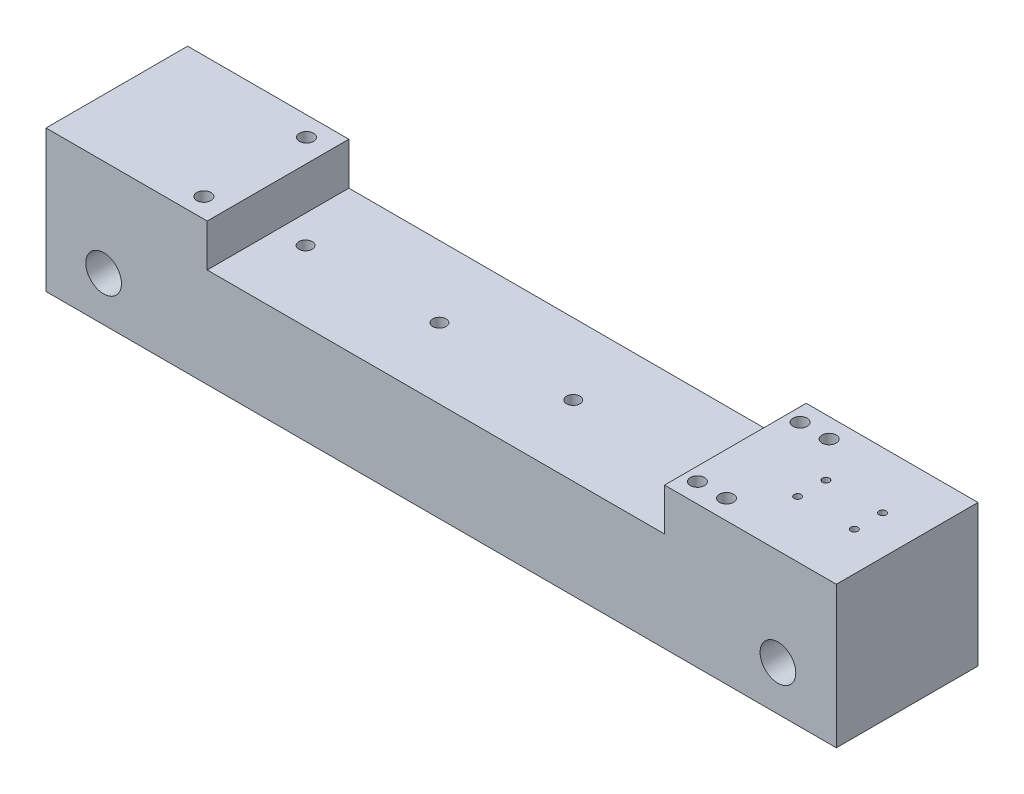
SolidWorks part; units mm, degrees
material "McMaster Steel"
ref_plane "Front Plane" through (0, 0, 0) normal (0, 0, 1) x (1, 0, 0)
ref_plane "Top Plane" through (0, 0, 0) normal (0, 1, 0) x (1, 0, 0)
ref_plane "Right Plane" through (0, 0, 0) normal (1, 0, 0) x (0, 0, -1)
sketch "Sketch1" plane through (0, 0, 0) normal (0, 0, 1) x (1, 0, 0)
  line L0 (177.125, 59) -> (177.125, 63.5)
  line L1 (177.125, 63.5) -> (100.125, 63.5)
  line L2 (100.125, 63.5) -> (100.125, 59)
  line L3 (100.125, 44.5) -> (-104.875, 44.5)
  line L4 (-2.375, 44.5) -> (-2.375, 40)
  line L5 (-104.875, 63.5) -> (-177.125, 63.5)
  line L6 (-177.125, 63.5) -> (-177.125, 59)
  line L7 (-104.875, 63.5) -> (-104.875, 59)
  circle A0 centre (164.385, 33.435) radius 2.6035
  circle A1 centre (169.95, 20) radius 2.6035
  circle A2 centre (164.385, 6.565) radius 2.6035
  circle A3 centre (137.515, 6.565) radius 2.6035
  circle A4 centre (131.95, 20) radius 2.6035
  circle A5 centre (137.515, 33.435) radius 2.6035
  circle A6 centre (-137.865, 33.435) radius 2.6035
  circle A7 centre (-132.3, 20) radius 2.6035
  circle A8 centre (-137.865, 6.565) radius 2.6035
  circle A9 centre (-164.735, 6.565) radius 2.6035
  circle A10 centre (-170.3, 20) radius 2.6035
  circle A11 centre (-164.735, 33.435) radius 2.6035
  line B0 (-177.125, 0) -> (177.125, 0)
  line B1 (177.125, 0) -> (177.125, 59)
  line B2 (177.125, 59) -> (100.125, 59)
  line B3 (100.125, 59) -> (100.125, 40)
  line B4 (100.125, 40) -> (-104.875, 40)
  line B5 (-104.875, 40) -> (-104.875, 59)
  line B6 (-104.875, 59) -> (-177.125, 59)
  line B7 (-177.125, 59) -> (-177.125, 0)
  circle B8 centre (-151.3, 20) radius 14
  circle B9 centre (150.95, 20) radius 14
  arc B10 (-164.735, 9.315) -> (-164.735, 3.815) centre (-164.735, 6.565) ccw
  arc B11 (-164.735, 9.315) -> (-164.735, 3.815) centre (-164.735, 6.565) ccw
  arc B12 (-164.735, 3.815) -> (-164.735, 9.315) centre (-164.735, 6.565) ccw
  arc B13 (-164.735, 3.815) -> (-164.735, 9.315) centre (-164.735, 6.565) ccw
  arc B14 (-137.865, 3.815) -> (-137.865, 9.315) centre (-137.865, 6.565) ccw
  arc B15 (-137.865, 3.815) -> (-137.865, 9.315) centre (-137.865, 6.565) ccw
  arc B16 (-137.865, 9.315) -> (-137.865, 3.815) centre (-137.865, 6.565) ccw
  arc B17 (-137.865, 9.315) -> (-137.865, 3.815) centre (-137.865, 6.565) ccw
  arc B18 (-132.3, 17.25) -> (-132.3, 22.75) centre (-132.3, 20) ccw
  arc B19 (-132.3, 17.25) -> (-132.3, 22.75) centre (-132.3, 20) ccw
  arc B20 (-132.3, 22.75) -> (-132.3, 17.25) centre (-132.3, 20) ccw
  arc B21 (-132.3, 22.75) -> (-132.3, 17.25) centre (-132.3, 20) ccw
  arc B22 (-137.865, 30.685) -> (-137.865, 36.185) centre (-137.865, 33.435) ccw
  arc B23 (-137.865, 30.685) -> (-137.865, 36.185) centre (-137.865, 33.435) ccw
  arc B24 (-137.865, 36.185) -> (-137.865, 30.685) centre (-137.865, 33.435) ccw
  arc B25 (-137.865, 36.185) -> (-137.865, 30.685) centre (-137.865, 33.435) ccw
  arc B26 (-170.3, 17.25) -> (-170.3, 22.75) centre (-170.3, 20) ccw
  arc B27 (-170.3, 17.25) -> (-170.3, 22.75) centre (-170.3, 20) ccw
  arc B28 (-170.3, 22.75) -> (-170.3, 17.25) centre (-170.3, 20) ccw
  arc B29 (-170.3, 22.75) -> (-170.3, 17.25) centre (-170.3, 20) ccw
  arc B30 (-164.735, 30.685) -> (-164.735, 36.185) centre (-164.735, 33.435) ccw
  arc B31 (-164.735, 30.685) -> (-164.735, 36.185) centre (-164.735, 33.435) ccw
  arc B32 (-164.735, 36.185) -> (-164.735, 30.685) centre (-164.735, 33.435) ccw
  arc B33 (-164.735, 36.185) -> (-164.735, 30.685) centre (-164.735, 33.435) ccw
  arc B34 (137.515, 9.315) -> (137.515, 3.815) centre (137.515, 6.565) ccw
  arc B35 (137.515, 9.315) -> (137.515, 3.815) centre (137.515, 6.565) ccw
  arc B36 (137.515, 3.815) -> (137.515, 9.315) centre (137.515, 6.565) ccw
  arc B37 (137.515, 3.815) -> (137.515, 9.315) centre (137.515, 6.565) ccw
  arc B38 (164.385, 9.315) -> (164.385, 3.815) centre (164.385, 6.565) ccw
  arc B39 (164.385, 9.315) -> (164.385, 3.815) centre (164.385, 6.565) ccw
  arc B40 (164.385, 3.815) -> (164.385, 9.315) centre (164.385, 6.565) ccw
  arc B41 (164.385, 3.815) -> (164.385, 9.315) centre (164.385, 6.565) ccw
  arc B42 (169.95, 17.25) -> (169.95, 22.75) centre (169.95, 20) ccw
  arc B43 (169.95, 17.25) -> (169.95, 22.75) centre (169.95, 20) ccw
  arc B44 (169.95, 22.75) -> (169.95, 17.25) centre (169.95, 20) ccw
  arc B45 (169.95, 22.75) -> (169.95, 17.25) centre (169.95, 20) ccw
  arc B46 (164.385, 30.685) -> (164.385, 36.185) centre (164.385, 33.435) ccw
  arc B47 (164.385, 30.685) -> (164.385, 36.185) centre (164.385, 33.435) ccw
  arc B48 (164.385, 36.185) -> (164.385, 30.685) centre (164.385, 33.435) ccw
  arc B49 (164.385, 36.185) -> (164.385, 30.685) centre (164.385, 33.435) ccw
  arc B50 (131.95, 17.25) -> (131.95, 22.75) centre (131.95, 20) ccw
  arc B51 (131.95, 17.25) -> (131.95, 22.75) centre (131.95, 20) ccw
  arc B52 (131.95, 22.75) -> (131.95, 17.25) centre (131.95, 20) ccw
  arc B53 (131.95, 22.75) -> (131.95, 17.25) centre (131.95, 20) ccw
  arc B54 (137.515, 30.685) -> (137.515, 36.185) centre (137.515, 33.435) ccw
  arc B55 (137.515, 30.685) -> (137.515, 36.185) centre (137.515, 33.435) ccw
  arc B56 (137.515, 36.185) -> (137.515, 30.685) centre (137.515, 33.435) ccw
  arc B57 (137.515, 36.185) -> (137.515, 30.685) centre (137.515, 33.435) ccw
  dimension "D1" = 5.207
  dimension "D2" = 63.5
sketch_block_instance "Block-SecondaryBlock Sideview-1"
sketch_block "Block-SecondaryBlock Sideview"
extrude "Boss-Extrude1" add sketch "Sketch1" along normal blind 63.5 contours B6 B7 B0 B1 B2 B3 B4 B5 B56 B54 B52 B50 B48 B46 B44 B42 B40 B38 B36 B34 B32 B30 B28 B26 B24 B22 B20 B18 B16 B14 B12 B10 B9 B8 | B46 B48 A0 | B54 B56 A5 | B42 B44 A1 | B38 B40 A2 | B50 B52 A4 | B34 B36 A3 | B22 B24 A6 | B18 B20 A7 | B14 B16 A8 | B10 B12 A9 | B26 B28 A10 | B30 B32 A11 | B2 L0 L1 L2 | B4 B3 L3 L4 | B6 L7 L5 L6 | B5 B4 L4 L3 region at (138.625, 61.25, 0) region at (0.6144, 25.4009, 0) region at (48.875, 42.25, 0) region at (-141, 61.25, 0) region at (-53.625, 42.25, 0) region at (-162.0628, 6.565, 0) region at (-140.5372, 6.565, 0) region at (-134.9722, 20, 0) region at (-140.5372, 33.435, 0) region at (-172.9722, 20, 0) region at (-167.4072, 33.435, 0) region at (140.1872, 6.565, 0) region at (167.0572, 6.565, 0) region at (167.2778, 20, 0) region at (161.7128, 33.435, 0) region at (129.2778, 20, 0) region at (134.8428, 33.435, 0)
sketch "Sketch2" plane through (0, 63.5, 0) normal (0, 1, 0) x (1, 0, 0)
  line L0 (177.125, -61.75) -> (177.125, -1.75)
  line L2 (177.125, -63.5) -> (177.125, 0) construction
  circle A0 centre (119.125, -54.75) radius 3.175
  circle A1 centre (106.125, -54.75) radius 3.175
  circle A2 centre (119.125, -8.75) radius 3.175
  circle A3 centre (106.125, -8.75) radius 3.175
  circle A4 centre (-115.125, -54.75) radius 3.175
  circle A5 centre (-115.125, -8.75) radius 3.175
  point P13 (177.125, -31.75)
  point P20 (177.125, -31.75)
  line B0 (-177.125, -1.75) -> (177.125, -1.75)
  line B1 (177.125, -1.75) -> (177.125, -41.55)
  line B2 (177.125, -41.55) -> (-177.125, -41.55) construction
  line B3 (-177.125, -41.55) -> (-177.125, -1.75)
  line B4 (-177.125, -41.55) -> (-177.125, -61.75)
  line B5 (-177.125, -61.75) -> (177.125, -61.75)
  line B6 (177.125, -61.75) -> (177.125, -41.55)
  arc B7 (-118.425, -8.75) -> (-111.825, -8.75) centre (-115.125, -8.75) ccw
  arc B8 (-111.825, -8.75) -> (-118.425, -8.75) centre (-115.125, -8.75) ccw
  arc B9 (-118.425, -54.75) -> (-111.825, -54.75) centre (-115.125, -54.75) ccw
  arc B10 (-111.825, -54.75) -> (-118.425, -54.75) centre (-115.125, -54.75) ccw
  arc B11 (-132.725, -34.65) -> (-128.525, -34.65) centre (-130.625, -34.65) ccw
  arc B12 (-128.525, -34.65) -> (-132.725, -34.65) centre (-130.625, -34.65) ccw
  arc B13 (-132.725, -8.65) -> (-128.525, -8.65) centre (-130.625, -8.65) ccw
  arc B14 (-128.525, -8.65) -> (-132.725, -8.65) centre (-130.625, -8.65) ccw
  arc B15 (-173.725, -34.65) -> (-169.525, -34.65) centre (-171.625, -34.65) ccw
  arc B16 (-169.525, -34.65) -> (-173.725, -34.65) centre (-171.625, -34.65) ccw
  arc B17 (-173.725, -8.65) -> (-169.525, -8.65) centre (-171.625, -8.65) ccw
  arc B18 (-169.525, -8.65) -> (-173.725, -8.65) centre (-171.625, -8.65) ccw
  arc B19 (128.525, -8.65) -> (132.725, -8.65) centre (130.625, -8.65) ccw
  arc B20 (132.725, -8.65) -> (128.525, -8.65) centre (130.625, -8.65) ccw
  arc B21 (169.525, -8.65) -> (173.725, -8.65) centre (171.625, -8.65) ccw
  arc B22 (173.725, -8.65) -> (169.525, -8.65) centre (171.625, -8.65) ccw
  arc B23 (169.525, -34.65) -> (173.725, -34.65) centre (171.625, -34.65) ccw
  arc B24 (173.725, -34.65) -> (169.525, -34.65) centre (171.625, -34.65) ccw
  arc B25 (128.525, -34.65) -> (132.725, -34.65) centre (130.625, -34.65) ccw
  arc B26 (132.725, -34.65) -> (128.525, -34.65) centre (130.625, -34.65) ccw
  arc B27 (115.825, -54.75) -> (122.425, -54.75) centre (119.125, -54.75) ccw
  arc B28 (122.425, -54.75) -> (115.825, -54.75) centre (119.125, -54.75) ccw
  arc B29 (102.825, -54.75) -> (109.425, -54.75) centre (106.125, -54.75) ccw
  arc B30 (109.425, -54.75) -> (102.825, -54.75) centre (106.125, -54.75) ccw
  arc B31 (115.825, -8.75) -> (122.425, -8.75) centre (119.125, -8.75) ccw
  arc B32 (122.425, -8.75) -> (115.825, -8.75) centre (119.125, -8.75) ccw
  arc B33 (102.825, -8.75) -> (109.425, -8.75) centre (106.125, -8.75) ccw
  arc B34 (109.425, -8.75) -> (102.825, -8.75) centre (106.125, -8.75) ccw
  dimension "D1" = 6.35
sketch_block_instance "Block-SecondaryBlock Topview-1"
sketch_block "Block-SecondaryBlock Topview"
extrude "Cut-Extrude1" cut sketch "Sketch2" against normal blind 19.05 contours A0 | A1 | A2 | A3 | A4 | A5 region at (119.125, 63.5, 54.75) region at (106.125, 63.5, 54.75) region at (119.125, 63.5, 8.75) region at (106.125, 63.5, 8.75) region at (-115.125, 63.5, 54.75) region at (-115.125, 63.5, 8.75)
extrude "Cut-Extrude3" cut sketch "Sketch2<3>" along normal blind 6.35 from surface contours B23 B24 | B25 B26 | B19 B20 | B21 B22 | B11 B12 | B13 B14 | B17 B18 | B15 B16 region at (-130.625, 63.5, 34.65) region at (-130.625, 63.5, 8.65) region at (-171.625, 63.5, 34.65) region at (-171.625, 63.5, 8.65) region at (130.625, 63.5, 8.65) region at (171.625, 63.5, 8.65) region at (171.625, 63.5, 34.65) region at (130.625, 63.5, 34.65) starting at face at (0, 0, 31.75)
sketch "Sketch2<3>" plane through (0, 63.5, 0) normal (0, 1, 0) x (1, 0, 0) same geometry as "Sketch2"
sketch "Sketch3" plane through (0, 0, 0) normal (0, 0, -1) x (-1, 0, 0)
  circle A1 centre (-150.95, 20) radius 8
  circle A3 centre (-150.95, 20) radius 14
  circle A4 centre (-150.95, 20) radius 14 construction
  circle A5 centre (151.3, 20) radius 8
  circle A6 centre (151.3, 20) radius 14
  circle A7 centre (151.3, 20) radius 14 construction
  dimension "D2" = 16
extrude "Boss-Extrude2" add sketch "Sketch3" along normal offset from surface (31.5 mm away) 32 from surface up to face at (164.95, 20, 0) starting at face at (164.95, 20, 63.5)
sketch "Sketch4" plane through (0, 63.5, 0) normal (0, 1, 0) x (1, 0, 0)
  line L0 (177.125, -63.5) -> (177.125, 0) construction
  point P1 (100.125, -31.75)
  point P5 (177.125, -31.75)
  line B0 (177.125, -1.75) -> (100.125, -1.75)
  line B1 (100.125, -1.75) -> (100.125, -61.75)
  line B2 (100.125, -61.75) -> (177.125, -61.75)
  line B3 (177.125, -61.75) -> (177.125, -1.75)
  line B4 (128.025, -22.25) -> (128.025, -41.25) construction
  line B5 (128.025, -22.25) -> (166.125, -22.25) construction
  line B6 (128.025, -41.25) -> (166.125, -41.25) construction
  line B7 (166.125, -22.25) -> (166.125, -41.25) construction
  circle B8 centre (134.375, -38.075) radius 1.5875
  circle B9 centre (134.375, -25.425) radius 1.5875
  circle B10 centre (159.775, -25.425) radius 1.5875
  circle B11 centre (159.775, -38.075) radius 1.5875
sketch_block_instance "Block-MotorMounting TopView 2-1"
sketch_block "Block-MotorMounting TopView 2"
extrude "Cut-Extrude4" cut sketch "Sketch4" against normal blind 6.35 contours B11 | B10 | B9 | B8 region at (134.375, 63.5, 38.075) region at (134.375, 63.5, 25.425) region at (159.775, 63.5, 25.425) region at (159.775, 63.5, 38.075)
sketch "Sketch5" plane through (0, 0, 63.5) normal (0, 0, 1) x (1, 0, 0)
  circle A0 centre (131.95, 20) radius 2.6035 construction
  circle A1 centre (137.515, 6.565) radius 2.6035 construction
  circle A2 centre (164.385, 6.565) radius 2.6035 construction
  circle A3 centre (169.95, 20) radius 2.6035 construction
  circle A4 centre (164.385, 33.435) radius 2.6035 construction
  circle A5 centre (137.515, 33.435) radius 2.6035 construction
  circle A6 centre (-137.865, 6.565) radius 2.6035 construction
  circle A7 centre (-132.3, 20) radius 2.6035 construction
  circle A8 centre (-137.865, 33.435) radius 2.6035 construction
  circle A9 centre (-164.735, 6.565) radius 2.6035 construction
  circle A10 centre (-170.3, 20) radius 2.6035 construction
  circle A11 centre (-164.735, 33.435) radius 2.6035 construction
  circle A12 centre (131.95, 20) radius 2.6035
  circle A13 centre (137.515, 6.565) radius 2.6035
  circle A14 centre (164.385, 6.565) radius 2.6035
  circle A15 centre (169.95, 20) radius 2.6035
  circle A16 centre (164.385, 33.435) radius 2.6035
  circle A17 centre (137.515, 33.435) radius 2.6035
  circle A18 centre (-137.865, 6.565) radius 2.6035
  circle A19 centre (-132.3, 20) radius 2.6035
  circle A20 centre (-137.865, 33.435) radius 2.6035
  circle A21 centre (-164.735, 6.565) radius 2.6035
  circle A22 centre (-170.3, 20) radius 2.6035
  circle A23 centre (-164.735, 33.435) radius 2.6035
extrude "Boss-Extrude3" add sketch "Sketch5" against normal offset from surface (50.8 mm away) 12.7 up to face at (164.95, 20, 0)
sketch "Sketch6" plane through (0, 44.5, 0) normal (0, 1, 0) x (1, 0, 0)
  line B0 (-104.875, -25.8312) -> (-104.875, -38.0188)
  line B1 (-104.875, -38.0188) -> (100.125, -38.0188)
  line B2 (100.125, -38.0188) -> (100.125, -25.8312)
  line B3 (100.125, -25.8312) -> (-104.875, -25.8312)
  line B4 (100.125, 0) -> (-104.875, 0)
  line B5 (-104.875, 0) -> (-104.875, -63.5)
  line B6 (-104.875, -63.5) -> (100.125, -63.5)
  line B7 (100.125, -63.5) -> (100.125, 0)
  arc B8 (27.625, -34.925) -> (27.625, -28.925) centre (27.625, -31.925) ccw
  arc B9 (27.625, -28.925) -> (27.625, -34.925) centre (27.625, -31.925) ccw
  arc B10 (87.625, -34.925) -> (87.625, -28.925) centre (87.625, -31.925) ccw
  arc B11 (87.625, -28.925) -> (87.625, -34.925) centre (87.625, -31.925) ccw
  arc B12 (-32.3698, -34.925) -> (-32.3698, -28.925) centre (-32.3698, -31.925) ccw
  arc B13 (-32.3698, -28.925) -> (-32.3698, -34.925) centre (-32.3698, -31.925) ccw
  arc B14 (-92.3646, -34.925) -> (-92.3646, -28.925) centre (-92.3646, -31.925) ccw
  arc B15 (-92.3646, -28.925) -> (-92.3646, -34.925) centre (-92.3646, -31.925) ccw
sketch_block_instance "Block-CarriageMountingTop-1"
sketch_block "Block-CarriageMountingTop" parameters "D1"=60
extrude "Cut-Extrude5" cut sketch "Sketch6" against normal blind 6.35 contours B10 B11 | B8 B9 | B12 B13 | B14 B15 region at (27.625, 44.5, 31.925) region at (87.625, 44.5, 31.925) region at (-32.3698, 44.5, 31.925) region at (-92.3646, 44.5, 31.925)
fillet "Fillet1" [suppressed] radius 1.27
